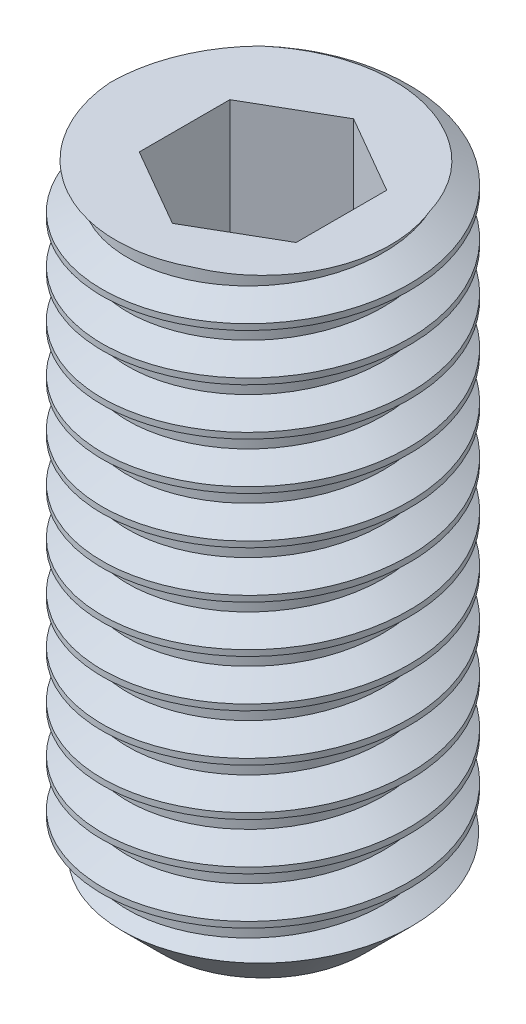
SolidWorks part; units mm, degrees
ref_plane "Front Plane" through (0, 0, 0) normal (0, 0, 1) x (1, 0, 0)
ref_plane "Top Plane" through (0, 0, 0) normal (0, 1, 0) x (1, 0, 0)
ref_plane "Right Plane" through (0, 0, 0) normal (1, 0, 0) x (0, 0, -1)
sketch "Sketch1" plane through (0, 0, 0) normal (0, 1, 0) x (1, 0, 0)
  circle A0 centre (0, 0) radius 1.465
  dimension "D1" = 2.93
extrude "Boss-Extrude1" add sketch "Sketch1" along normal blind 6
chamfer "Chamfer1" distance 0.5 angle 45 1 edges at (0, 0, 1.465)
sketch "Sketch2" plane through (0, 6, 0) normal (0, 1, 0) x (1, 0, 0)
  line L1 (0, -0.866) -> (0.75, -0.433)
  line L2 (0.75, -0.433) -> (0.75, 0.433)
  line L3 (0.75, 0.433) -> (0, 0.866)
  line L4 (0, 0.866) -> (-0.75, 0.433)
  line L5 (-0.75, 0.433) -> (-0.75, -0.433)
  line L6 (-0.75, -0.433) -> (0, -0.866)
  circle A0 centre (0, 0) radius 0.75 construction
  dimension "D1" = 1.5
extrude "Cut-Extrude1" cut sketch "Sketch2" against normal blind 1.5
thread "Thread1" pitch 0.45 method cut profile "Thread Profile1" start angle 0, offset 0.45, length 0, pitch 0.45, diameter 2.93
ref_plane "Plane1" through (-1.465, 6.45, 0) normal (0, 0, 1) x (-1, 0, 0)
sketch "Thread Profile1" plane through (-1.465, 6.45, 0) normal (0, 0, 1) x (-1, 0, 0)
  line L0 (0, 0) -> (0, 0.45) construction
  line L11 (0, 0) -> (0, 0.3937)
  line L12 (0, 0.3937) -> (-0.2436, 0.2531)
  line L13 (-0.2436, 0.2531) -> (-0.2436, 0.1406)
  line L15 (-0.2436, 0.1406) -> (0, 0)
  line L17 (-0.2436, 0.1969) -> (0, 0.1969) construction
  point P2 (0, 0)
  dimension "Pitch" = 0.45
  dimension "Profile_Angle" = 60
  dimension "Profile_Land" = 0.1125
  dimension "Profile_Height" = 0.2436
